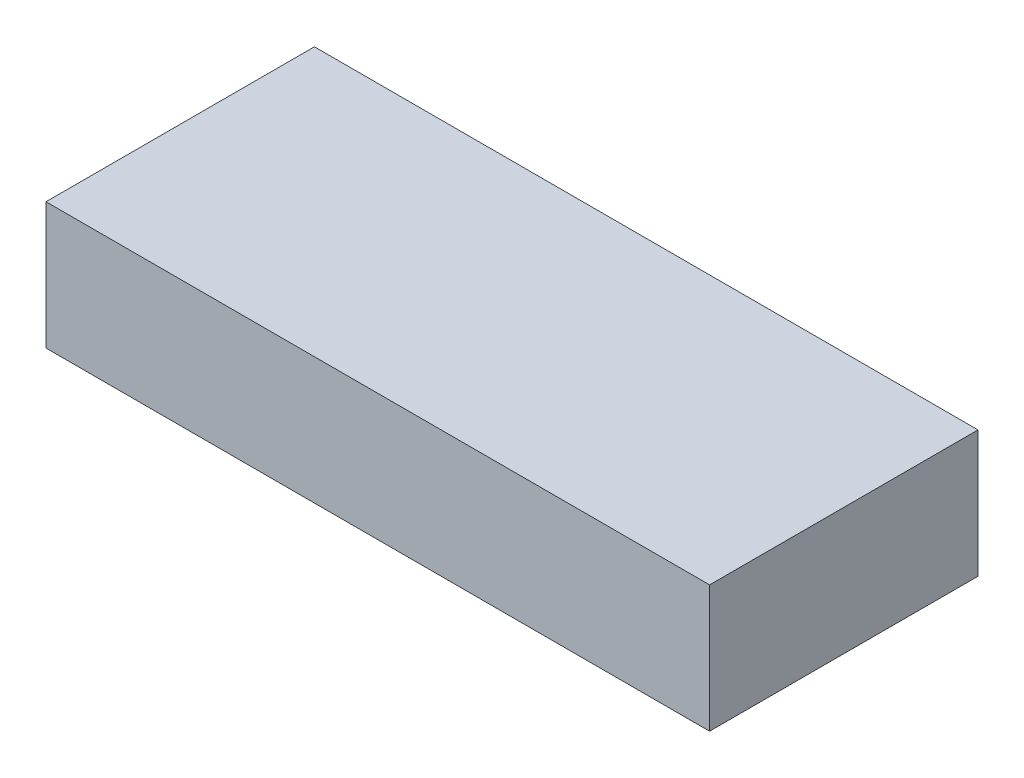
SolidWorks part; units mm, degrees
ref_plane "Alzado" through (0, 0, 0) normal (0, 0, 1) x (1, 0, 0)
ref_plane "Planta" through (0, 0, 0) normal (0, 1, 0) x (1, 0, 0)
ref_plane "Vista lateral" through (0, 0, 0) normal (1, 0, 0) x (0, 0, -1)
sketch "Croquis1" plane through (0, 0, 0) normal (0, 1, 0) x (1, 0, 0)
  line L1 (44.5, 18) -> (-44.5, 18)
  line L2 (44.5, 18) -> (44.5, -18)
  line L3 (44.5, -18) -> (-44.5, -18)
  line L4 (-44.5, 18) -> (-44.5, -18)
  line L5 (44.5, 18) -> (-44.5, -18) construction
  line L6 (44.5, -18) -> (-44.5, 18) construction
  point P0 (0, 0)
  dimension "D1" = 89
  dimension "D2" = 36
extrude "Saliente-Extruir1" add sketch "Croquis1" along normal blind 4.6
sketch "Croquis2" plane through (0, 4.6, 0) normal (0, 1, 0) x (1, 0, 0)
  line L4 (-44.5, 18) -> (-44.5, -18)
  line L5 (-44.5, -18) -> (44.5, -18)
  line L6 (44.5, -18) -> (44.5, 18)
  line L7 (44.5, 18) -> (-44.5, 18)
  line L8 (-44.5, 18) -> (-44.5, -18)
  line L9 (-44.5, -18) -> (44.5, -18)
  line L10 (44.5, -18) -> (44.5, 18)
  line L11 (44.5, 18) -> (-44.5, 18)
  dimension "D1" = 0
extrude "Saliente-Extruir2" add sketch "Croquis2" along normal blind 12.4
